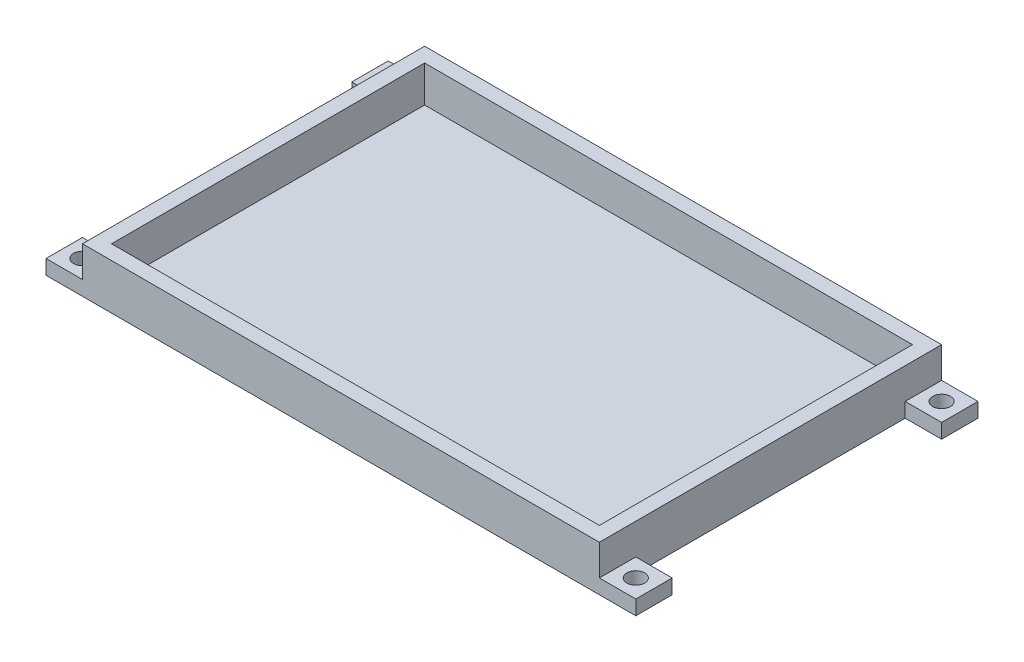
SolidWorks part; units mm, degrees
ref_plane "Front Plane" through (0, 0, 0) normal (0, 0, 1) x (1, 0, 0)
ref_plane "Top Plane" through (0, 0, 0) normal (0, 1, 0) x (1, 0, 0)
ref_plane "Right Plane" through (0, 0, 0) normal (1, 0, 0) x (0, 0, -1)
sketch "Sketch1" plane through (0, 0, 0) normal (0, 1, 0) x (1, 0, 0)
  line L0 (-2.54, 57.15) -> (87.63, 57.15)
  line L1 (0, 0) -> (85.09, 0)
  line L2 (0, 0) -> (0, 54.61)
  line L3 (0, 54.61) -> (85.09, 54.61)
  line L4 (85.09, 0) -> (85.09, 54.61)
  line L5 (87.63, 57.15) -> (87.63, -2.54)
  line L6 (87.63, -2.54) -> (-2.54, -2.54)
  line L7 (-2.54, -2.54) -> (-2.54, 57.15)
  dimension "D1" = 85.09
  dimension "D2" = 54.61
  dimension "D3" = 2.54
  dimension "D4" = 2.54
  dimension "D5" = 2.54
  dimension "D6" = 2.54
extrude "Boss-Extrude1" add sketch "Sketch1" along normal blind 6.35
sketch "Sketch2" plane through (0, 0, 0) normal (0, -1, 0) x (1, 0, 0)
  line L1 (87.63, -57.15) -> (-2.54, -57.15)
  line L2 (87.63, -57.15) -> (87.63, 2.54)
  line L3 (87.63, 2.54) -> (-2.54, 2.54)
  line L4 (-2.54, -57.15) -> (-2.54, 2.54)
extrude "Boss-Extrude2" add sketch "Sketch2" along normal blind 1.5875
sketch "Sketch3" plane through (0, -1.5875, 0) normal (0, -1, 0) x (1, 0, 0)
  line L0 (87.63, -57.15) -> (87.63, 2.54) construction
  line L1 (87.63, -50.8) -> (93.98, -50.8)
  line L2 (87.63, -50.8) -> (87.63, -57.15)
  line L3 (87.63, -57.15) -> (93.98, -57.15)
  line L4 (93.98, -50.8) -> (93.98, -57.15)
  line L5 (-2.54, -57.15) -> (87.63, -57.15) construction
  line L6 (-2.54, -27.305) -> (87.63, -27.305) construction
  line L7 (-2.54, 2.54) -> (-2.54, -57.15) construction
  line L8 (42.545, 2.54) -> (42.545, -57.15) construction
  line L9 (87.63, 2.54) -> (-2.54, 2.54) construction
  line L10 (-8.89, -50.8) -> (-8.89, -57.15)
  line L11 (-2.54, -57.15) -> (-8.89, -57.15)
  line L12 (-2.54, -50.8) -> (-2.54, -57.15)
  line L13 (-2.54, -50.8) -> (-8.89, -50.8)
  line L14 (87.63, -50.8) -> (93.98, -50.8)
  line L15 (87.63, -50.8) -> (87.63, -57.15)
  line L16 (87.63, -57.15) -> (93.98, -57.15)
  line L17 (93.98, -50.8) -> (93.98, -57.15)
  line L18 (-8.89, -50.8) -> (-8.89, -57.15)
  line L19 (-2.54, -57.15) -> (-8.89, -57.15)
  line L20 (-2.54, -50.8) -> (-2.54, -57.15)
  line L21 (-2.54, -50.8) -> (-8.89, -50.8)
  line L22 (-2.54, -3.81) -> (-8.89, -3.81)
  line L23 (-2.54, -3.81) -> (-2.54, 2.54)
  line L24 (-2.54, 2.54) -> (-8.89, 2.54)
  line L25 (-8.89, -3.81) -> (-8.89, 2.54)
  line L26 (93.98, -3.81) -> (93.98, 2.54)
  line L27 (87.63, 2.54) -> (93.98, 2.54)
  line L28 (87.63, -3.81) -> (87.63, 2.54)
  line L29 (87.63, -3.81) -> (93.98, -3.81)
  line L30 (-2.54, -3.81) -> (-8.89, -3.81)
  line L31 (-2.54, -3.81) -> (-2.54, 2.54)
  line L32 (-2.54, 2.54) -> (-8.89, 2.54)
  line L33 (-8.89, -3.81) -> (-8.89, 2.54)
  line L34 (93.98, -3.81) -> (93.98, 2.54)
  line L35 (87.63, 2.54) -> (93.98, 2.54)
  line L36 (87.63, -3.81) -> (87.63, 2.54)
  line L37 (87.63, -3.81) -> (93.98, -3.81)
  circle A0 centre (90.805, -53.975) radius 1.55
  circle A1 centre (-5.715, -53.975) radius 1.55
  circle A2 centre (90.805, -53.975) radius 1.55
  circle A3 centre (-5.715, -53.975) radius 1.55
  circle A4 centre (-5.715, -0.635) radius 1.55
  circle A5 centre (90.805, -0.635) radius 1.55
  circle A6 centre (-5.715, -0.635) radius 1.55
  circle A7 centre (90.805, -0.635) radius 1.55
  line M6 (87.63, -57.15) -> (87.63, 2.54)
  line M8 (-2.54, 2.54) -> (-2.54, -57.15)
  dimension "D4" = 3.1
  dimension "D1" = 6.35
  dimension "D2" = 6.35
  dimension "D3" = 0
  dimension "D5" = 3.175
  dimension "D6" = 3.175
extrude "Boss-Extrude3" add sketch "Sketch3" against normal blind 2.54 contours L29 L26 L27 A5 M6 | L25 L22 L24 A4 M8 | L13 L10 L11 A1 M8 | L4 L1 L3 A0 M6 region at (90.805, -1.5875, -50.8898) region at (87.7198, -1.5875, -0.635) region at (-5.715, -1.5875, -50.8898) region at (-5.715, -1.5875, -3.7202)
